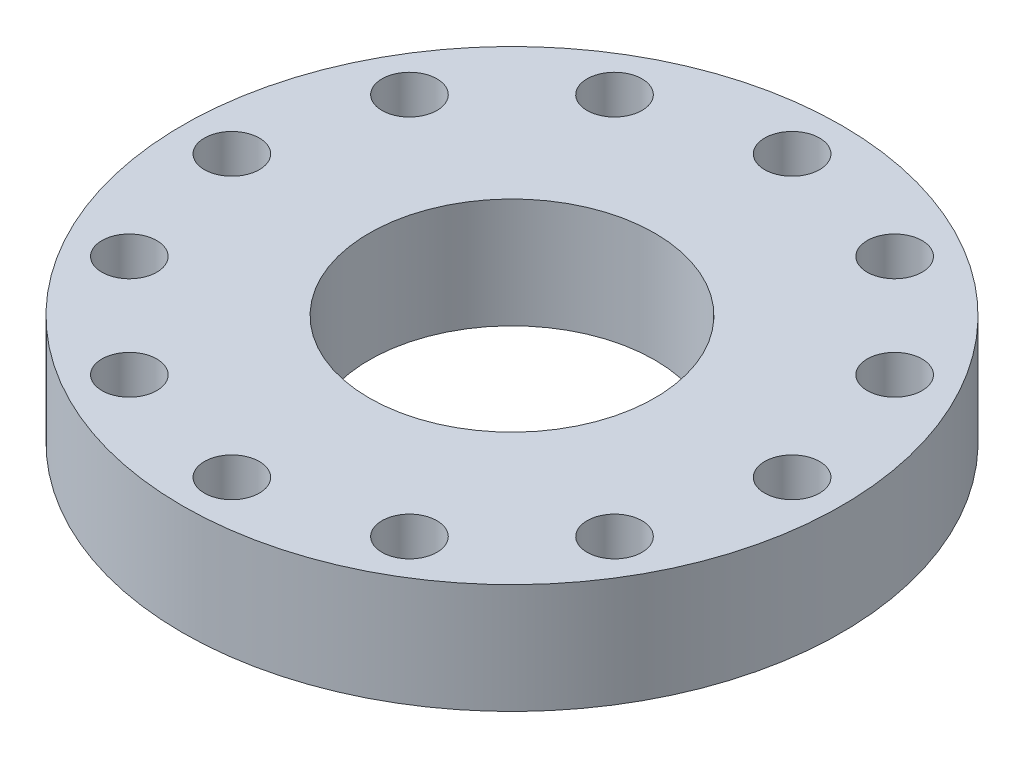
SolidWorks part; units mm, degrees
ref_plane "Front Plane" through (0, 0, 0) normal (0, 0, 1) x (1, 0, 0)
ref_plane "Top Plane" through (0, 0, 0) normal (0, 1, 0) x (1, 0, 0)
ref_plane "Right Plane" through (0, 0, 0) normal (1, 0, 0) x (0, 0, -1)
sketch "Sketch1" plane through (0, 0, 0) normal (0, 1, 0) x (1, 0, 0)
  circle A0 centre (0, 0) radius 30
  circle A1 centre (0, 0) radius 25.5 construction
  circle A2 centre (0, 25.5) radius 2.5
  circle A3 centre (12.75, 22.0836) radius 2.5
  circle A4 centre (22.0836, 12.75) radius 2.5
  circle A5 centre (25.5, 0) radius 2.5
  circle A6 centre (22.0836, -12.75) radius 2.5
  circle A7 centre (12.75, -22.0836) radius 2.5
  circle A8 centre (0, 0) radius 13
  circle A9 centre (0, -25.5) radius 2.5
  circle A10 centre (-12.75, -22.0836) radius 2.5
  circle A11 centre (-22.0836, -12.75) radius 2.5
  circle A12 centre (-25.5, 0) radius 2.5
  circle A13 centre (-22.0836, 12.75) radius 2.5
  circle A14 centre (-12.75, 22.0836) radius 2.5
  point P18 (0, 0)
  dimension "D1" = 51
  dimension "D2" = 5
  dimension "D4" = 60
  dimension "D5" = 26
  dimension "D3" = 12
extrude "Boss-Extrude1" add sketch "Sketch1" along normal blind 10
